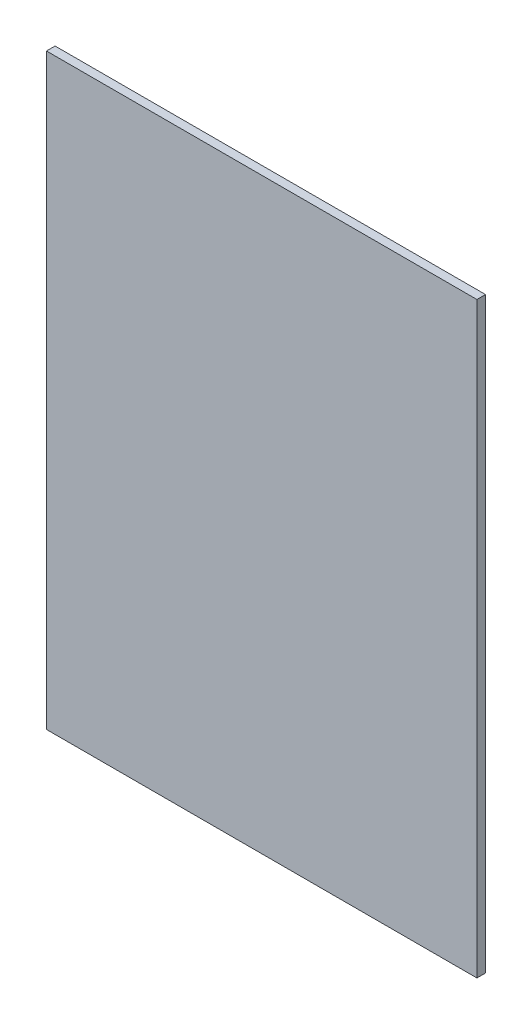
SolidWorks part; units mm, degrees
ref_plane "前视基准面" through (0, 0, 0) normal (0, 0, 1) x (1, 0, 0)
ref_plane "上视基准面" through (0, 0, 0) normal (0, 1, 0) x (1, 0, 0)
ref_plane "右视基准面" through (0, 0, 0) normal (1, 0, 0) x (0, 0, -1)
sketch "草图1" plane through (0, 0, 0) normal (0, 0, 1) x (1, 0, 0)
  line L1 (-50, 68.25) -> (50, 68.25)
  line L2 (-50, 68.25) -> (-50, -68.25)
  line L3 (-50, -68.25) -> (50, -68.25)
  line L4 (50, 68.25) -> (50, -68.25)
  line L5 (-50, 68.25) -> (50, -68.25) construction
  line L6 (-50, -68.25) -> (50, 68.25) construction
  point P0 (0, 0)
  dimension "D1" = 100
  dimension "D2" = 136.5
base flange "基体-法兰1" sketch "草图1" thickness 2 reverse thickness direction no parameters "D1"=1
sketch "折弯-线1" plane through (0, 0, 0) normal (0, 1, 0) x (1, 0, 0)
sketch "边界框1" plane through (0, 0, 0) normal (0, 1, 0) x (1, 0, 0)
sheet metal parameters "钣金6" thickness 2 parameters "D1"=1
flat pattern "平板型式6" [suppressed]
sketch "折弯-线2" plane through (0, 0, 0) normal (0, 1, 0) x (1, 0, 0)
sketch "边界框2" [suppressed] plane through (0, 0, 0) normal (0, 1, 0) x (1, 0, 0)
